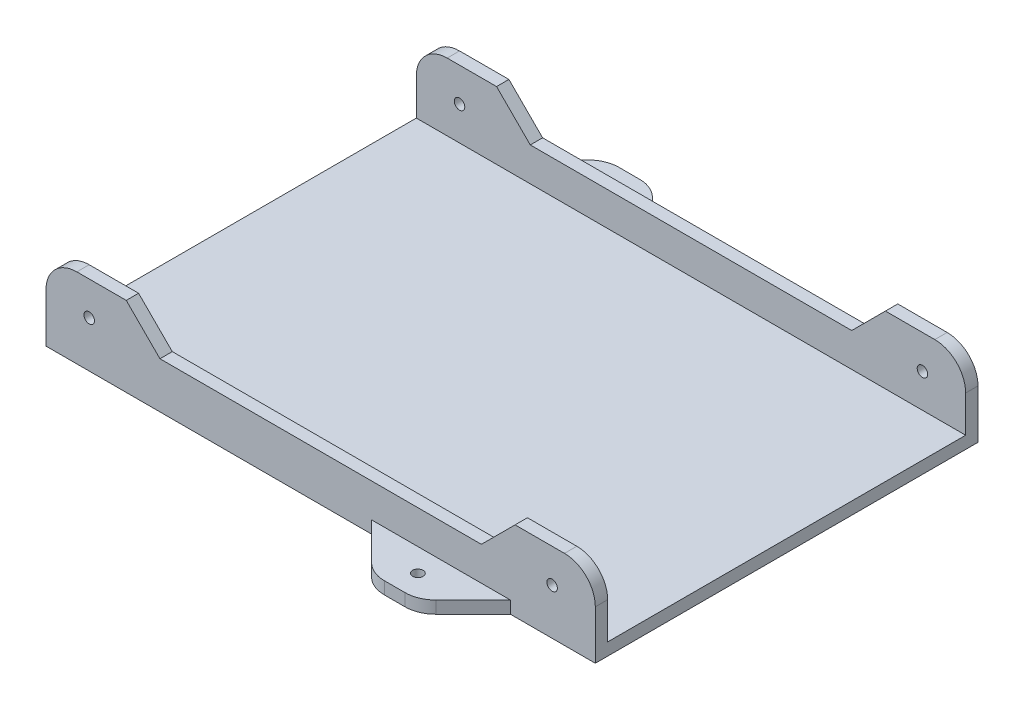
SolidWorks part; units mm, degrees
ref_plane "Front Plane" through (0, 0, 0) normal (0, 0, 1) x (1, 0, 0)
ref_plane "Top Plane" through (0, 0, 0) normal (0, 1, 0) x (1, 0, 0)
ref_plane "Right Plane" through (0, 0, 0) normal (1, 0, 0) x (0, 0, -1)
sketch "Sketch1" plane through (0, 0, 0) normal (0, 0, 1) x (1, 0, 0)
  line L1 (0, 0) -> (178, 0)
  line L2 (0, 0) -> (0, 21.844)
  line L3 (0, 21.844) -> (178, 21.844)
  line L4 (178, 0) -> (178, 21.844)
  line L5 (0, 0) -> (178, 0)
  line L6 (0, 0) -> (0, -4)
  line L7 (0, -4) -> (178, -4)
  line L8 (178, 0) -> (178, -4)
  circle A0 centre (14, 10.922) radius 1.7
  circle A1 centre (164, 10.922) radius 1.7
  dimension "D6" = 3.4
  dimension "D1" = 10.922
  dimension "D2" = 150
  dimension "D3" = 14
  dimension "D4" = 14
  dimension "D5" = 10.922
  dimension "D7" = 4
extrude "Boss-Extrude1" add sketch "Sketch1" along normal blind 4 contours L8 L1 L6 L7 | L1 L4 L3 L2 A1 A0 region at (89, 10.922, 0) region at (89, -2, 0)
extrude "Boss-Extrude2" add sketch "Sketch1<3>" against normal blind 116 contours L8 L1 L6 L7 region at (89, -2, 0)
sketch "Sketch1<3>" plane through (0, 0, 0) normal (0, 0, 1) x (1, 0, 0) same geometry as "Sketch1"
sketch "Sketch2" plane through (0, 0, -116) normal (0, 0, -1) x (-1, 0, 0)
  line L0 (-178, 0) -> (-178, -4) construction
  line L1 (-178, -4) -> (0, -4) construction
  line L2 (0, -4) -> (0, 0) construction
  line L3 (0, 0) -> (-178, 0) construction
  line L4 (-178, 0) -> (0, 0) construction
  line L5 (0, 0) -> (0, 21.844) construction
  line L6 (0, 21.844) -> (-178, 21.844) construction
  line L7 (-178, 21.844) -> (-178, 0) construction
  line L8 (-178, 0) -> (-178, -4)
  line L9 (-178, -4) -> (0, -4)
  line L10 (0, -4) -> (0, 0)
  line L11 (0, 0) -> (-178, 0)
  line L12 (-178, 0) -> (0, 0)
  line L13 (0, 0) -> (0, 21.844)
  line L14 (0, 21.844) -> (-178, 21.844)
  line L15 (-178, 21.844) -> (-178, 0)
  circle A0 centre (-14, 10.922) radius 1.7 construction
  circle A1 centre (-164, 10.922) radius 1.7 construction
  circle A2 centre (-14, 10.922) radius 1.7
  circle A3 centre (-164, 10.922) radius 1.7
  line M1 (-178, 0) -> (-178, -4)
  line M2 (-178, -4) -> (0, -4)
  line M3 (0, -4) -> (0, 0)
  line M4 (0, 0) -> (-178, 0)
extrude "Boss-Extrude3" add sketch "Sketch2" along normal blind 4 contours M4 M1 M2 M3 | L14 L15 L13 A3 A2 M4 region at (89, -2, -116) region at (89, 10.922, -116)
fillet "Fillet1" radius 10 4 edges at (0, 21.844, -118) (0, 21.844, 2) (178, 21.844, -118) (178, 21.844, 2)
sketch "Sketch3" plane through (0, -4, 0) normal (0, -1, 0) x (1, 0, 0)
  line L0 (0, 4) -> (178, 4) construction
  line L1 (135.5, 4) -> (120.5, 4)
  line L2 (135.5, 4) -> (135.5, 19)
  line L3 (135.5, 19) -> (120.5, 19)
  line L4 (120.5, 4) -> (120.5, 19)
  line L10 (135.5, 19) -> (150.5, 4)
  line L11 (120.5, 19) -> (105.5, 4)
  line L12 (178, 4) -> (178, -120) construction
  line L13 (89, 4) -> (89, -120) construction
  line L14 (178, -120) -> (0, -120) construction
  line L15 (178, -58) -> (0, -58) construction
  line L16 (0, 4) -> (0, -120) construction
  line L17 (120.5, -135) -> (105.5, -120) construction
  line L18 (135.5, -135) -> (150.5, -120) construction
  line L19 (120.5, -120) -> (120.5, -135) construction
  line L20 (135.5, -135) -> (120.5, -135) construction
  line L21 (135.5, -120) -> (135.5, -135) construction
  line L22 (135.5, -120) -> (120.5, -120) construction
  line L23 (42.5, -120) -> (57.5, -120)
  line L24 (42.5, -120) -> (42.5, -135)
  line L25 (42.5, -135) -> (57.5, -135)
  line L26 (57.5, -120) -> (57.5, -135)
  line L27 (42.5, -135) -> (27.5, -120)
  line L28 (57.5, -135) -> (72.5, -120)
  circle A0 centre (128, 11.5) radius 1.7
  circle A1 centre (128, -127.5) radius 1.7 construction
  circle A2 centre (50, -127.5) radius 1.7
  point P6 (135.5, 11.5)
  point P7 (128, 19)
  point P14 (89, 4)
  point P16 (178, -58)
  point P32 (128, -135)
  point P33 (135.5, -127.5)
  point P42 (42.5, -127.5)
  point P43 (50, -135)
  line M15 (0, -120) -> (178, -120)
  line M17 (178, 4) -> (0, 4)
  dimension "D1" = 3.4
  dimension "D6" = 50
  dimension "D2" = 15
  dimension "D3" = 15
  dimension "D4" = 45
  dimension "D5" = 45
extrude "Boss-Extrude4" add sketch "Sketch3" against normal blind 4 contours L27 L24 M15 | L26 L24 L25 A2 M15 | L26 L28 M15 | L4 L11 M17 | L4 L2 L3 A0 M17 | L10 L2 M17 region at (128, -4, 4.2121) region at (140.5, -4, 9) region at (115.5, -4, 9) region at (50, -4, -120.2121) region at (37.5, -4, -125) region at (62.5, -4, -125)
fillet "Fillet2" radius 10 4 edges at (42.5, -2, -135) (57.5, -2, -135) (120.5, -2, 19) (135.5, -2, 19)
sketch "Sketch4" plane through (0, 0, -120) normal (0, 0, -1) x (-1, 0, 0)
  line L0 (-152, 21.844) -> (-141.078, 10.922)
  line L1 (-10, 21.844) -> (-168, 21.844) construction
  line L2 (-141.078, 10.922) -> (-36.922, 10.922)
  line L3 (-89, 10.922) -> (-89, 21.844) construction
  line L4 (-26, 21.844) -> (-36.922, 10.922)
  line L5 (-152, 21.844) -> (-26, 21.844)
  circle A0 centre (-164, 10.922) radius 1.7 construction
  circle A1 centre (-164, 10.922) radius 1.7
  point P5 (-89, 21.844)
  dimension "D1" = 12
  dimension "D2" = 135
extrude "Cut-Extrude1" cut sketch "Sketch4" against normal through all both and the other way through all
equation "\"D5@Sketch1\"=\"D1@Sketch1\""
